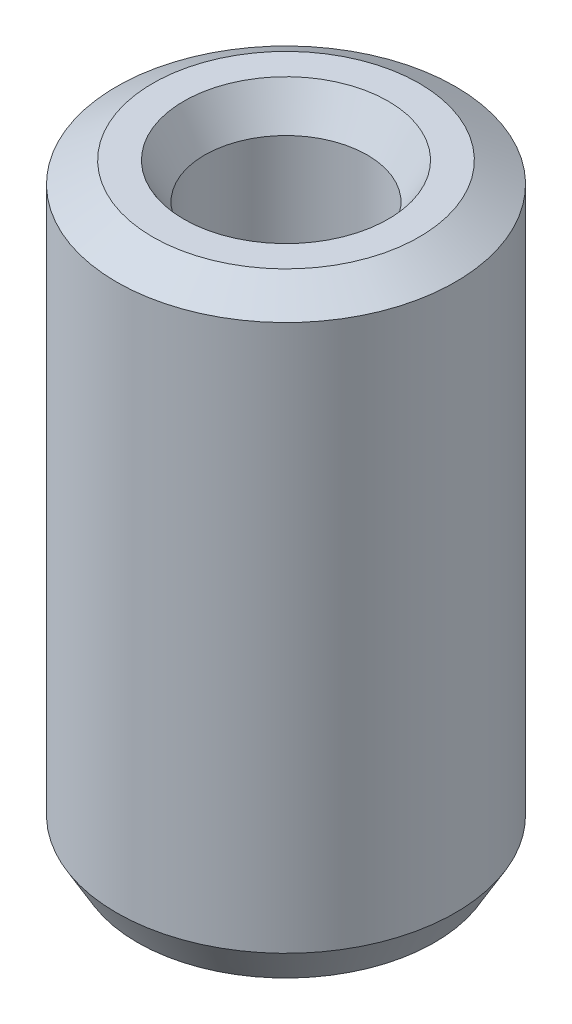
SolidWorks part; units mm, degrees
ref_plane "Front Plane" through (0, 0, 0) normal (0, 0, 1) x (1, 0, 0)
ref_plane "Top Plane" through (0, 0, 0) normal (0, 1, 0) x (1, 0, 0)
ref_plane "Right Plane" through (0, 0, 0) normal (1, 0, 0) x (0, 0, -1)
sketch "Sketch1" plane through (0, 0, 0) normal (0, 1, 0) x (1, 0, 0)
  circle A0 centre (0, 0) radius 30
  dimension "SLEEVE_OD" = 60
extrude "Boss-Extrude1" add sketch "Sketch1" along normal blind 106.8554
sketch "Sketch2" plane through (0, 0, 0) normal (0, 1, 0) x (1, 0, 0)
  circle A0 centre (0, 0) radius 14.407
  dimension "BORE_D" = 28.814
extrude "Cut-Extrude1" cut sketch "Sketch2" along normal through all
chamfer "Chamfer1" distance 3.6992 angle 60 4 edges at (0, 106.8554, 14.407) (0, 0, 14.407) (0, 0, 30) (0, 106.8554, 30) first distance on face at (0, 106.8554, 14.407) first distance on face at (0, 0, 14.407) first distance on face at (0, 106.8554, 30)
